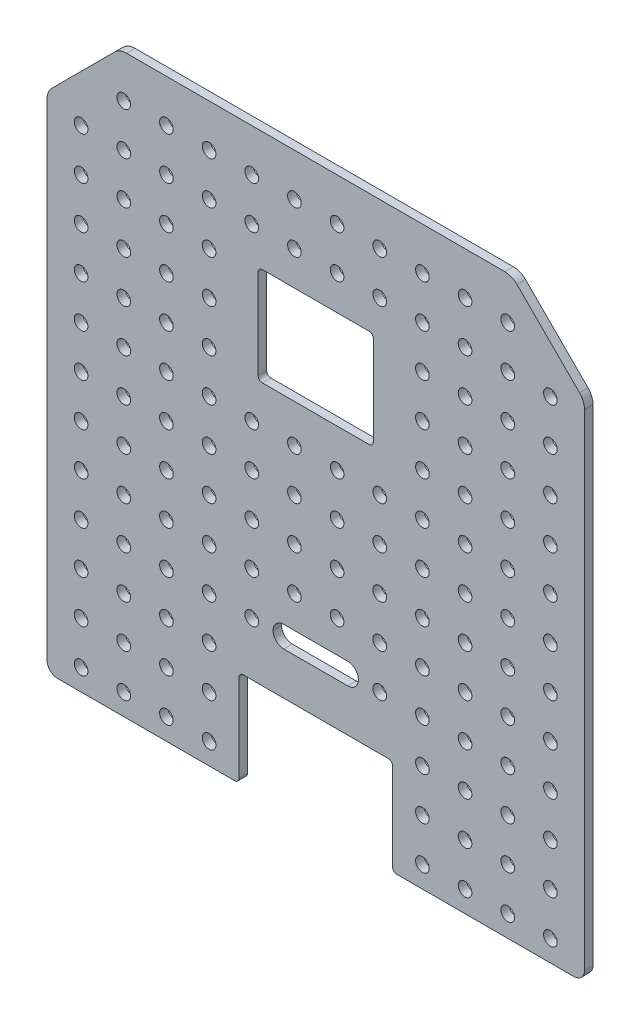
SolidWorks part; units mm, degrees
ref_plane "Front" through (0, 0, 0) normal (0, 0, 1) x (1, 0, 0)
ref_plane "Top" through (0, 0, 0) normal (0, 1, 0) x (1, 0, 0)
ref_plane "Right" through (0, 0, 0) normal (1, 0, 0) x (0, 0, -1)
sketch "Эскиз1" plane through (0, 0, 0) normal (0, 0, 1) x (1, 0, 0)
  line L0 (-63, 0) -> (63, 0)
  line L1 (63, 0) -> (63, -135)
  line L3 (63, -135) -> (-63, -135)
  line L5 (-63, -135) -> (-63, 0)
  point P3 (0, 0)
  point P7 (0, -135)
  dimension "D1" = 126
  dimension "D2" = 135
extrude "Основа" add sketch "Эскиз1" along normal blind 2
sketch "Эскиз3" plane through (0, 0, 0) normal (0, 0, -1) x (-1, 0, 0)
  line L0 (63, -135) -> (-63, -135) construction
  line L2 (-13.5, -28) -> (-13.5, -51)
  line L3 (-13.5, -51) -> (13.5, -51)
  line L4 (13.5, -28) -> (13.5, -51)
  line L7 (13.5, -28) -> (-13.5, -28)
  point P4 (0, -28)
  point P6 (0, 0)
  point P8 (13, -27.46)
  point P10 (0, -51)
  point P12 (13, -37.54)
  point P13 (0, 0)
  point P15 (-13, -28.8983)
  dimension "D1" = 23
  dimension "D2" = 27
  dimension "D3" = 84
extrude "Окошко для доступа к шилду" cut sketch "Эскиз3" against normal through all
sketch "Эскиз4" plane through (0, 0, 0) normal (0, 0, -1) x (-1, 0, 0)
  line L0 (63, -135) -> (-63, -135) construction
  line L1 (-18, -112.5) -> (18, -112.5)
  line L2 (-18, -112.5) -> (-18, -135)
  line L3 (-18, -135) -> (18, -135)
  line L4 (18, -112.5) -> (18, -135)
  point P6 (0, -135)
  dimension "D1" = 22.5
  dimension "D2" = 36
extrude "Под объектив камеры" cut sketch "Эскиз4" against normal through all
chamfer "Фаска1" distance 17 1 edges at (-63, 0, 1)
chamfer "Фаска2" distance 17 1 edges at (63, 0, 1)
sketch "Эскиз2" plane through (0, 0, 0) normal (0, 0, -1) x (-1, 0, 0)
  line L0 (0, 0) -> (0, -135) construction
  line L1 (63, -135) -> (18, -135) construction
  line L2 (-18, -135) -> (-63, -135) construction
  circle A0 centre (5, -130) radius 1.6 construction
  circle A1 centre (15, -130) radius 1.6 construction
  circle A2 centre (25, -130) radius 1.6
  circle A3 centre (35, -130) radius 1.6
  circle A4 centre (45, -130) radius 1.6
  circle A5 centre (55, -130) radius 1.6
  circle A6 centre (65, -130) radius 1.6
  circle A7 centre (75, -130) radius 1.6 construction
  circle A8 centre (-75, -130) radius 1.6 construction
  circle A9 centre (-65, -130) radius 1.6
  circle A10 centre (-55, -130) radius 1.6
  circle A11 centre (-45, -130) radius 1.6
  circle A12 centre (-35, -130) radius 1.6
  circle A13 centre (-25, -130) radius 1.6
  circle A14 centre (-15, -130) radius 1.6 construction
  circle A15 centre (-5, -130) radius 1.6 construction
  circle A16 centre (5, -120) radius 1.6 construction
  circle A17 centre (15, -120) radius 1.6 construction
  circle A18 centre (25, -120) radius 1.6
  circle A19 centre (35, -120) radius 1.6
  circle A20 centre (45, -120) radius 1.6
  circle A21 centre (55, -120) radius 1.6
  circle A22 centre (65, -120) radius 1.6
  circle A23 centre (75, -120) radius 1.6 construction
  circle A24 centre (-75, -120) radius 1.6 construction
  circle A25 centre (-65, -120) radius 1.6
  circle A26 centre (-55, -120) radius 1.6
  circle A27 centre (-45, -120) radius 1.6
  circle A28 centre (-35, -120) radius 1.6
  circle A29 centre (-25, -120) radius 1.6
  circle A30 centre (-15, -120) radius 1.6 construction
  circle A31 centre (-5, -120) radius 1.6 construction
  circle A32 centre (5, -110) radius 1.6 construction
  circle A33 centre (15, -110) radius 1.6 construction
  circle A34 centre (25, -110) radius 1.6
  circle A35 centre (35, -110) radius 1.6
  circle A36 centre (45, -110) radius 1.6
  circle A37 centre (55, -110) radius 1.6
  circle A38 centre (65, -110) radius 1.6
  circle A39 centre (75, -110) radius 1.6 construction
  circle A40 centre (-75, -110) radius 1.6 construction
  circle A41 centre (-65, -110) radius 1.6
  circle A42 centre (-55, -110) radius 1.6
  circle A43 centre (-45, -110) radius 1.6
  circle A44 centre (-35, -110) radius 1.6
  circle A45 centre (-25, -110) radius 1.6
  circle A46 centre (-15, -110) radius 1.6 construction
  circle A47 centre (-5, -110) radius 1.6 construction
  circle A48 centre (5, -100) radius 1.6
  circle A49 centre (15, -100) radius 1.6
  circle A50 centre (25, -100) radius 1.6
  circle A51 centre (35, -100) radius 1.6
  circle A52 centre (45, -100) radius 1.6
  circle A53 centre (55, -100) radius 1.6
  circle A54 centre (65, -100) radius 1.6
  circle A55 centre (75, -100) radius 1.6 construction
  circle A56 centre (-75, -100) radius 1.6 construction
  circle A57 centre (-65, -100) radius 1.6
  circle A58 centre (-55, -100) radius 1.6
  circle A59 centre (-45, -100) radius 1.6
  circle A60 centre (-35, -100) radius 1.6
  circle A61 centre (-25, -100) radius 1.6
  circle A62 centre (-15, -100) radius 1.6
  circle A63 centre (-5, -100) radius 1.6
  circle A64 centre (5, -90) radius 1.6
  circle A65 centre (15, -90) radius 1.6
  circle A66 centre (25, -90) radius 1.6
  circle A67 centre (35, -90) radius 1.6
  circle A68 centre (45, -90) radius 1.6
  circle A69 centre (55, -90) radius 1.6
  circle A70 centre (65, -90) radius 1.6
  circle A71 centre (75, -90) radius 1.6 construction
  circle A72 centre (-75, -90) radius 1.6 construction
  circle A73 centre (-65, -90) radius 1.6
  circle A74 centre (-55, -90) radius 1.6
  circle A75 centre (-45, -90) radius 1.6
  circle A76 centre (-35, -90) radius 1.6
  circle A77 centre (-25, -90) radius 1.6
  circle A78 centre (-15, -90) radius 1.6
  circle A79 centre (-5, -90) radius 1.6
  circle A80 centre (5, -80) radius 1.6
  circle A81 centre (15, -80) radius 1.6
  circle A82 centre (25, -80) radius 1.6
  circle A83 centre (35, -80) radius 1.6
  circle A84 centre (45, -80) radius 1.6
  circle A85 centre (55, -80) radius 1.6
  circle A86 centre (65, -80) radius 1.6
  circle A87 centre (75, -80) radius 1.6 construction
  circle A88 centre (-75, -80) radius 1.6 construction
  circle A89 centre (-65, -80) radius 1.6
  circle A90 centre (-55, -80) radius 1.6
  circle A91 centre (-45, -80) radius 1.6
  circle A92 centre (-35, -80) radius 1.6
  circle A93 centre (-25, -80) radius 1.6
  circle A94 centre (-15, -80) radius 1.6
  circle A95 centre (-5, -80) radius 1.6
  circle A96 centre (5, -70) radius 1.6
  circle A97 centre (15, -70) radius 1.6
  circle A98 centre (25, -70) radius 1.6
  circle A99 centre (35, -70) radius 1.6
  circle A100 centre (45, -70) radius 1.6
  circle A101 centre (55, -70) radius 1.6
  circle A102 centre (65, -70) radius 1.6
  circle A103 centre (75, -70) radius 1.6 construction
  circle A104 centre (-75, -70) radius 1.6 construction
  circle A105 centre (-65, -70) radius 1.6
  circle A106 centre (-55, -70) radius 1.6
  circle A107 centre (-45, -70) radius 1.6
  circle A108 centre (-35, -70) radius 1.6
  circle A109 centre (-25, -70) radius 1.6
  circle A110 centre (-15, -70) radius 1.6
  circle A111 centre (-5, -70) radius 1.6
  circle A112 centre (5, -60) radius 1.6
  circle A113 centre (15, -60) radius 1.6
  circle A114 centre (25, -60) radius 1.6
  circle A115 centre (35, -60) radius 1.6
  circle A116 centre (45, -60) radius 1.6
  circle A117 centre (55, -60) radius 1.6
  circle A118 centre (65, -60) radius 1.6
  circle A119 centre (75, -60) radius 1.6 construction
  circle A120 centre (-75, -60) radius 1.6 construction
  circle A121 centre (-65, -60) radius 1.6
  circle A122 centre (-55, -60) radius 1.6
  circle A123 centre (-45, -60) radius 1.6
  circle A124 centre (-35, -60) radius 1.6
  circle A125 centre (-25, -60) radius 1.6
  circle A126 centre (-15, -60) radius 1.6
  circle A127 centre (-5, -60) radius 1.6
  circle A128 centre (5, -50) radius 1.6 construction
  circle A129 centre (15, -50) radius 1.6 construction
  circle A130 centre (25, -50) radius 1.6
  circle A131 centre (35, -50) radius 1.6
  circle A132 centre (45, -50) radius 1.6
  circle A133 centre (55, -50) radius 1.6
  circle A134 centre (65, -50) radius 1.6
  circle A135 centre (75, -50) radius 1.6 construction
  circle A136 centre (-75, -50) radius 1.6 construction
  circle A137 centre (-65, -50) radius 1.6
  circle A138 centre (-55, -50) radius 1.6
  circle A139 centre (-45, -50) radius 1.6
  circle A140 centre (-35, -50) radius 1.6
  circle A141 centre (-25, -50) radius 1.6
  circle A142 centre (-15, -50) radius 1.6 construction
  circle A143 centre (-5, -50) radius 1.6 construction
  circle A144 centre (5, -40) radius 1.6 construction
  circle A145 centre (15, -40) radius 1.6 construction
  circle A146 centre (25, -40) radius 1.6
  circle A147 centre (35, -40) radius 1.6
  circle A148 centre (45, -40) radius 1.6
  circle A149 centre (55, -40) radius 1.6
  circle A150 centre (65, -40) radius 1.6
  circle A151 centre (75, -40) radius 1.6 construction
  circle A152 centre (-75, -40) radius 1.6 construction
  circle A153 centre (-65, -40) radius 1.6
  circle A154 centre (-55, -40) radius 1.6
  circle A155 centre (-45, -40) radius 1.6
  circle A156 centre (-35, -40) radius 1.6
  circle A157 centre (-25, -40) radius 1.6
  circle A158 centre (-15, -40) radius 1.6 construction
  circle A159 centre (-5, -40) radius 1.6 construction
  circle A160 centre (5, -30) radius 1.6 construction
  circle A161 centre (15, -30) radius 1.6 construction
  circle A162 centre (25, -30) radius 1.6
  circle A163 centre (35, -30) radius 1.6
  circle A164 centre (45, -30) radius 1.6
  circle A165 centre (55, -30) radius 1.6
  circle A166 centre (65, -30) radius 1.6 construction
  circle A167 centre (75, -30) radius 1.6 construction
  circle A168 centre (-75, -30) radius 1.6 construction
  circle A169 centre (-65, -30) radius 1.6 construction
  circle A170 centre (-55, -30) radius 1.6
  circle A171 centre (-45, -30) radius 1.6
  circle A172 centre (-35, -30) radius 1.6
  circle A173 centre (-25, -30) radius 1.6
  circle A174 centre (-15, -30) radius 1.6 construction
  circle A175 centre (-5, -30) radius 1.6 construction
  circle A176 centre (5, -20) radius 1.6
  circle A177 centre (15, -20) radius 1.6
  circle A178 centre (25, -20) radius 1.6
  circle A179 centre (35, -20) radius 1.6
  circle A180 centre (45, -20) radius 1.6
  circle A181 centre (55, -20) radius 1.6
  circle A182 centre (65, -20) radius 1.6 construction
  circle A183 centre (75, -20) radius 1.6 construction
  circle A184 centre (-75, -20) radius 1.6 construction
  circle A185 centre (-65, -20) radius 1.6 construction
  circle A186 centre (-55, -20) radius 1.6
  circle A187 centre (-45, -20) radius 1.6
  circle A188 centre (-35, -20) radius 1.6
  circle A189 centre (-25, -20) radius 1.6
  circle A190 centre (-15, -20) radius 1.6
  circle A191 centre (-5, -20) radius 1.6
  circle A192 centre (5, -10) radius 1.6
  circle A193 centre (15, -10) radius 1.6
  circle A194 centre (25, -10) radius 1.6
  circle A195 centre (35, -10) radius 1.6
  circle A196 centre (45, -10) radius 1.6
  circle A197 centre (55, -10) radius 1.6 construction
  circle A198 centre (65, -10) radius 1.6 construction
  circle A199 centre (75, -10) radius 1.6 construction
  circle A200 centre (-75, -10) radius 1.6 construction
  circle A201 centre (-65, -10) radius 1.6 construction
  circle A202 centre (-55, -10) radius 1.6 construction
  circle A203 centre (-45, -10) radius 1.6
  circle A204 centre (-35, -10) radius 1.6
  circle A205 centre (-25, -10) radius 1.6
  circle A206 centre (-15, -10) radius 1.6
  circle A207 centre (-5, -10) radius 1.6
  circle A208 centre (5, 0) radius 1.6 construction
  circle A209 centre (15, 0) radius 1.6 construction
  circle A210 centre (25, 0) radius 1.6 construction
  circle A211 centre (35, 0) radius 1.6 construction
  circle A212 centre (45, 0) radius 1.6 construction
  circle A213 centre (55, 0) radius 1.6 construction
  circle A214 centre (65, 0) radius 1.6 construction
  circle A215 centre (75, 0) radius 1.6 construction
  circle A216 centre (-75, 0) radius 1.6 construction
  circle A217 centre (-65, 0) radius 1.6 construction
  circle A218 centre (-55, 0) radius 1.6 construction
  circle A219 centre (-45, 0) radius 1.6 construction
  circle A220 centre (-35, 0) radius 1.6 construction
  circle A221 centre (-25, 0) radius 1.6 construction
  circle A222 centre (-15, 0) radius 1.6 construction
  circle A223 centre (-5, 0) radius 1.6 construction
  circle A224 centre (5, 10) radius 1.6 construction
  circle A225 centre (15, 10) radius 1.6 construction
  circle A226 centre (25, 10) radius 1.6 construction
  circle A227 centre (35, 10) radius 1.6 construction
  circle A228 centre (45, 10) radius 1.6 construction
  circle A229 centre (55, 10) radius 1.6 construction
  circle A230 centre (65, 10) radius 1.6 construction
  circle A231 centre (75, 10) radius 1.6 construction
  circle A232 centre (-75, 10) radius 1.6 construction
  circle A233 centre (-65, 10) radius 1.6 construction
  circle A234 centre (-55, 10) radius 1.6 construction
  circle A235 centre (-45, 10) radius 1.6 construction
  circle A236 centre (-35, 10) radius 1.6 construction
  circle A237 centre (-25, 10) radius 1.6 construction
  circle A238 centre (-15, 10) radius 1.6 construction
  circle A239 centre (-5, 10) radius 1.6 construction
  circle A240 centre (5, 20) radius 1.6 construction
  circle A241 centre (15, 20) radius 1.6 construction
  circle A242 centre (25, 20) radius 1.6 construction
  circle A243 centre (35, 20) radius 1.6 construction
  circle A244 centre (45, 20) radius 1.6 construction
  circle A245 centre (55, 20) radius 1.6 construction
  circle A246 centre (65, 20) radius 1.6 construction
  circle A247 centre (75, 20) radius 1.6 construction
  circle A248 centre (-75, 20) radius 1.6 construction
  circle A249 centre (-65, 20) radius 1.6 construction
  circle A250 centre (-55, 20) radius 1.6 construction
  circle A251 centre (-45, 20) radius 1.6 construction
  circle A252 centre (-35, 20) radius 1.6 construction
  circle A253 centre (-25, 20) radius 1.6 construction
  circle A254 centre (-15, 20) radius 1.6 construction
  circle A255 centre (-5, 20) radius 1.6 construction
  circle A256 centre (5, 30) radius 1.6 construction
  circle A257 centre (15, 30) radius 1.6 construction
  circle A258 centre (25, 30) radius 1.6 construction
  circle A259 centre (35, 30) radius 1.6 construction
  circle A260 centre (45, 30) radius 1.6 construction
  circle A261 centre (55, 30) radius 1.6 construction
  circle A262 centre (65, 30) radius 1.6 construction
  circle A263 centre (75, 30) radius 1.6 construction
  circle A264 centre (-75, 30) radius 1.6 construction
  circle A265 centre (-65, 30) radius 1.6 construction
  circle A266 centre (-55, 30) radius 1.6 construction
  circle A267 centre (-45, 30) radius 1.6 construction
  circle A268 centre (-35, 30) radius 1.6 construction
  circle A269 centre (-25, 30) radius 1.6 construction
  circle A270 centre (-15, 30) radius 1.6 construction
  circle A271 centre (-5, 30) radius 1.6 construction
  circle A272 centre (5, 40) radius 1.6 construction
  circle A273 centre (15, 40) radius 1.6 construction
  circle A274 centre (25, 40) radius 1.6 construction
  circle A275 centre (35, 40) radius 1.6 construction
  circle A276 centre (45, 40) radius 1.6 construction
  circle A277 centre (55, 40) radius 1.6 construction
  circle A278 centre (65, 40) radius 1.6 construction
  circle A279 centre (75, 40) radius 1.6 construction
  circle A280 centre (-75, 40) radius 1.6 construction
  circle A281 centre (-65, 40) radius 1.6 construction
  circle A282 centre (-55, 40) radius 1.6 construction
  circle A283 centre (-45, 40) radius 1.6 construction
  circle A284 centre (-35, 40) radius 1.6 construction
  circle A285 centre (-25, 40) radius 1.6 construction
  circle A286 centre (-15, 40) radius 1.6 construction
  circle A287 centre (-5, 40) radius 1.6 construction
  circle A288 centre (5, 50) radius 1.6 construction
  circle A289 centre (15, 50) radius 1.6 construction
  circle A290 centre (25, 50) radius 1.6 construction
  circle A291 centre (35, 50) radius 1.6 construction
  circle A292 centre (45, 50) radius 1.6 construction
  circle A293 centre (55, 50) radius 1.6 construction
  circle A294 centre (65, 50) radius 1.6 construction
  circle A295 centre (75, 50) radius 1.6 construction
  circle A296 centre (-75, 50) radius 1.6 construction
  circle A297 centre (-65, 50) radius 1.6 construction
  circle A298 centre (-55, 50) radius 1.6 construction
  circle A299 centre (-45, 50) radius 1.6 construction
  circle A300 centre (-35, 50) radius 1.6 construction
  circle A301 centre (-25, 50) radius 1.6 construction
  circle A302 centre (-15, 50) radius 1.6 construction
  circle A303 centre (-5, 50) radius 1.6 construction
  circle A304 centre (5, 60) radius 1.6 construction
  circle A305 centre (15, 60) radius 1.6 construction
  circle A306 centre (25, 60) radius 1.6 construction
  circle A307 centre (35, 60) radius 1.6 construction
  circle A308 centre (45, 60) radius 1.6 construction
  circle A309 centre (55, 60) radius 1.6 construction
  circle A310 centre (65, 60) radius 1.6 construction
  circle A311 centre (75, 60) radius 1.6 construction
  circle A312 centre (-75, 60) radius 1.6 construction
  circle A313 centre (-65, 60) radius 1.6 construction
  circle A314 centre (-55, 60) radius 1.6 construction
  circle A315 centre (-45, 60) radius 1.6 construction
  circle A316 centre (-35, 60) radius 1.6 construction
  circle A317 centre (-25, 60) radius 1.6 construction
  circle A318 centre (-15, 60) radius 1.6 construction
  circle A319 centre (-5, 60) radius 1.6 construction
  dimension "D1" = 3.2
  dimension "D2" = 5
  dimension "D3" = 5
  dimension "D5" = 10
  dimension "D7" = 10
  dimension "D4" = 8
  dimension "D6" = 20
extrude "Сетка отв 10х10мм" cut sketch "Эскиз2" against normal through all
fillet "Скругление1" radius 1 8 edges at (-13.5, -51, 1) (13.5, -51, 1) (13.5, -28, 1) (-13.5, -28, 1) (18, -112.5, 1) (-18, -112.5, 1) (18, -135, 1) (-18, -135, 1)
fillet "Скругление3" radius 2.5 2 edges at (-63, -135, 1) (63, -135, 1)
fillet "Скругление2" radius 4 4 edges at (63, -17, 1) (-63, -17, 1) (46, 0, 1) (-46, 0, 1)
sketch "Эскиз5" plane through (0, 0, 2) normal (0, 0, 1) x (1, 0, 0)
  line L0 (19, -135) -> (60.5, -135) construction
  line L1 (-10, -97.5) -> (10, -97.5)
  line L2 (-10, -97.5) -> (-10, -102.5)
  line L3 (-10, -102.5) -> (10, -102.5)
  line L4 (10, -97.5) -> (10, -102.5)
  point P4 (0, -102.5)
  point P8 (10, -100)
  dimension "D1" = 5
  dimension "D2" = 20
  dimension "D3" = 35
extrude "Под шлейф камеры" cut sketch "Эскиз5" against normal through all
fillet "Скругление4" radius 2.5 4 edges at (10, -102.5, 1) (10, -97.5, 1) (-10, -102.5, 1) (-10, -97.5, 1)
